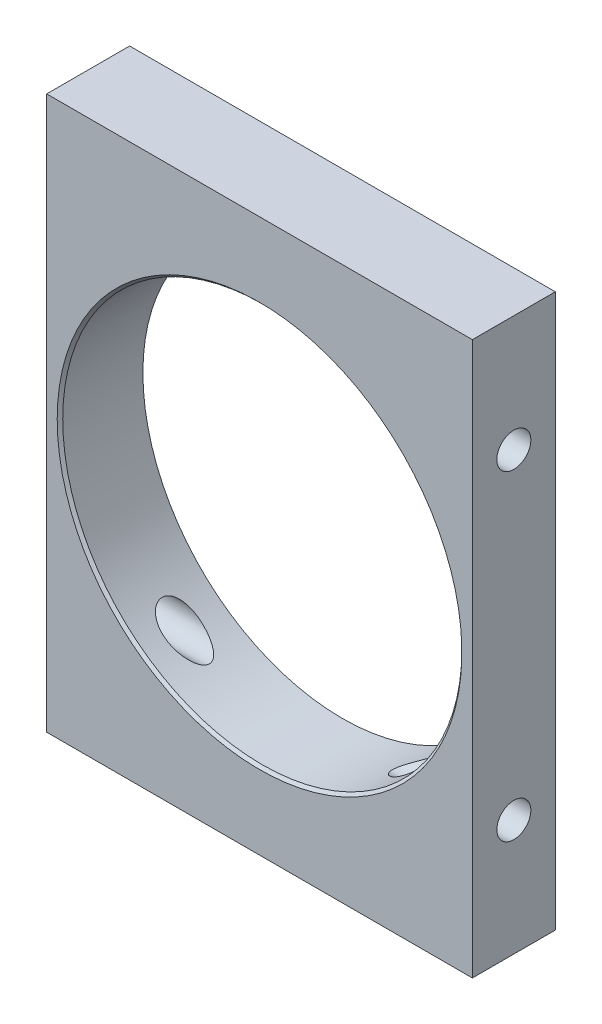
SolidWorks part; units mm, degrees
ref_plane "Ebene vorne" through (0, 0, 0) normal (0, 0, 1) x (1, 0, 0)
ref_plane "Ebene oben" through (0, 0, 0) normal (0, 1, 0) x (1, 0, 0)
ref_plane "Ebene rechts" through (0, 0, 0) normal (1, 0, 0) x (0, 0, -1)
sketch "Skizze1" plane through (0, 0, 0) normal (0, 0, 1) x (1, 0, 0)
  line L1 (-38.5, -50) -> (38.5, -50)
  line L2 (-38.5, -50) -> (-38.5, 50)
  line L3 (-38.5, 50) -> (38.5, 50)
  line L4 (38.5, -50) -> (38.5, 50)
  line L5 (-38.5, -50) -> (38.5, 50) construction
  line L6 (-38.5, 50) -> (38.5, -50) construction
  point P0 (0, 0)
  dimension "D1" = 77
  dimension "D2" = 100
extrude "Aufsatz-Linear austragen1" add sketch "Skizze1" along normal mid plane 15
sketch "Skizze2" plane through (0, 0, 7.5) normal (0, 0, 1) x (1, 0, 0)
  circle A0 centre (0, 0) radius 36.1
  dimension "D1" = 72.2
extrude "Schnitt-Linear austragen1" cut sketch "Skizze2" against normal through all
sketch "Skizze3" plane through (38.5, 0, 0) normal (1, 0, 0) x (0, 0, -1)
  line L0 (0, 0) -> (0, -50000) construction
  line L1 (0, 0) -> (26.9663, 0) construction
  circle A0 centre (0, 29) radius 3.075
  circle A1 centre (0, -29) radius 3.075
  dimension "D1" = 6.15
  dimension "D2" = 29
extrude "Schnitt-Linear austragen2" cut sketch "Skizze3" against normal through all
chamfer "Fase1" distance 0.5 angle 45 1 edges at (36.1, 0, 7.5)
